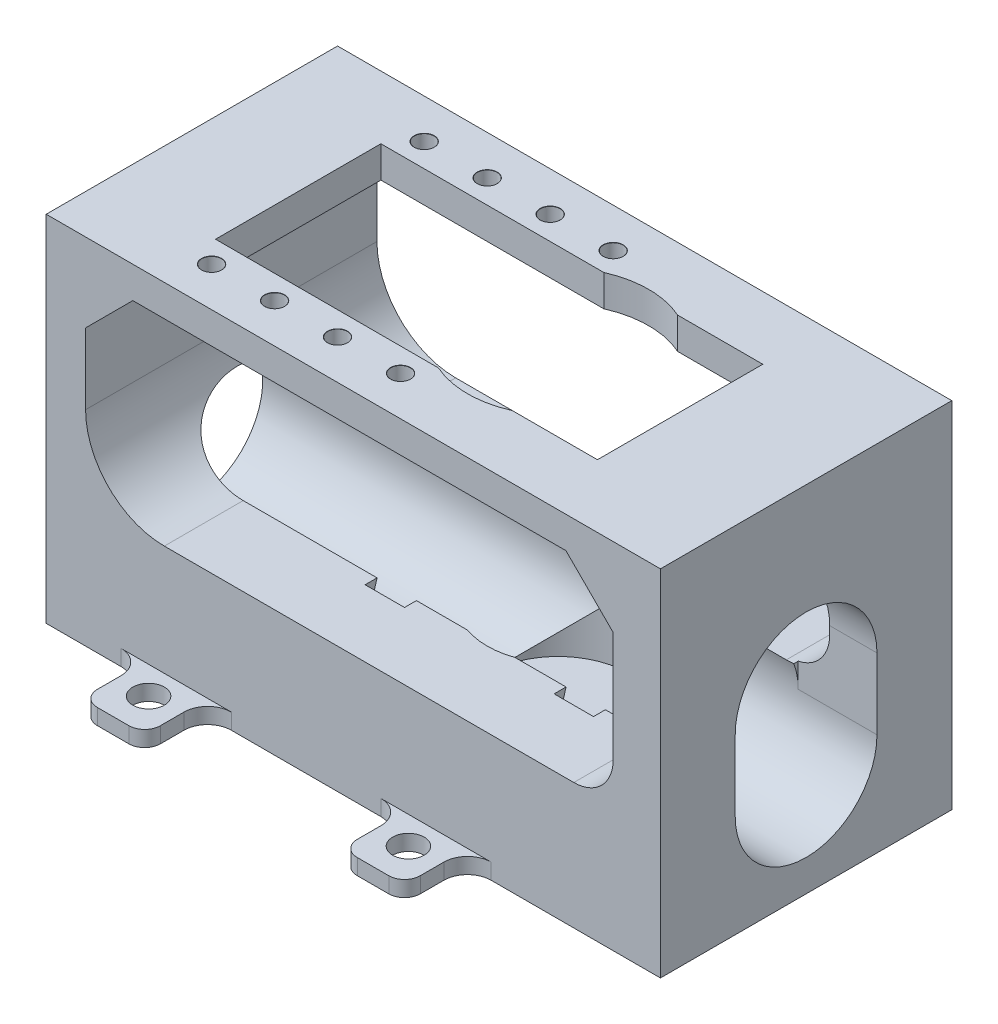
SolidWorks part; units mm, degrees
ref_plane "Front Plane" through (0, 0, 0) normal (0, 0, 1) x (1, 0, 0)
ref_plane "Top Plane" through (0, 0, 0) normal (0, 1, 0) x (1, 0, 0)
ref_plane "Right Plane" through (0, 0, 0) normal (1, 0, 0) x (0, 0, -1)
sketch "Sketch1" plane through (0, 0, 0) normal (0, 1, 0) x (1, 0, 0)
  line L1 (0, 0) -> (78, 0)
  line L2 (0, 0) -> (0, 37)
  line L3 (0, 37) -> (78, 37)
  line L4 (78, 0) -> (78, 37)
extrude "Boss-Extrude2" add sketch "Sketch1" along normal blind 2
sketch "Sketch4" plane through (0, 2, 0) normal (0, 1, 0) x (1, 0, 0)
  line L0 (78, 37) -> (0, 37) construction
  line L1 (0, 0) -> (5, 0)
  line L2 (0, 0) -> (0, 37)
  line L3 (0, 37) -> (5, 37)
  line L4 (5, 0) -> (5, 37)
extrude "Boss-Extrude3" add sketch "Sketch4" along normal blind 43
sketch "Sketch5" plane through (0, 2, 0) normal (0, 1, 0) x (1, 0, 0)
  line L0 (78, 37) -> (5, 37) construction
  line L1 (78, 0) -> (72, 0)
  line L2 (78, 0) -> (78, 37)
  line L3 (78, 37) -> (72, 37)
  line L4 (72, 0) -> (72, 37)
extrude "Boss-Extrude4" add sketch "Sketch5" along normal blind 43
sketch "Sketch6" plane through (0, 2, 0) normal (0, 1, 0) x (1, 0, 0)
  line L0 (72, 37) -> (72, 0) construction
  line L1 (5, 0) -> (72, 0)
  line L2 (5, 0) -> (5, 37)
  line L3 (5, 37) -> (72, 37)
  line L4 (72, 0) -> (72, 37)
extrude "Boss-Extrude5" add sketch "Sketch6" along normal blind 14 contours L2 L1 L4 L3
sketch "Sketch11" plane through (5, 0, 0) normal (1, 0, 0) x (0, 0, -1)
  line L1 (0, 41) -> (8, 41)
  line L2 (0, 41) -> (0, 45)
  line L3 (0, 45) -> (8, 45)
  line L4 (8, 41) -> (8, 45)
extrude "Boss-Extrude7" add sketch "Sketch11" along normal blind 67
sketch "Sketch14" plane through (72, 0, 0) normal (-1, 0, 0) x (0, 0, 1)
  line L1 (-37, 41) -> (-29, 41)
  line L2 (-37, 41) -> (-37, 45)
  line L3 (-37, 45) -> (-29, 45)
  line L4 (-29, 41) -> (-29, 45)
extrude "Boss-Extrude8" add sketch "Sketch14" along normal blind 67
sketch "Sketch15" plane through (0, 0, 0) normal (0, 0, 1) x (1, 0, 0)
  line L1 (0, 0) -> (78, 0) construction
  line L5 (12.5, 0) -> (12.5, 2)
  line L6 (12.5, 0) -> (20.5, 0)
  line L7 (12.5, 0) -> (12.5, 2)
  line L8 (12.5, 2) -> (20.5, 2)
  line L9 (20.5, 0) -> (20.5, 2)
  line L11 (20.5, 2) -> (20.5, 0)
  line L13 (45.5, 2) -> (45.5, 0)
  line L15 (45.5, 2) -> (53.5, 2)
  line L16 (45.5, 2) -> (45.5, 0)
  line L17 (45.5, 0) -> (53.5, 0)
  line L18 (53.5, 2) -> (53.5, 0)
  line M13 (0, 0) -> (78, 0)
extrude "Boss-Extrude9" add sketch "Sketch15" along normal blind 8 contours L9 L8 L5 M13 | L18 L15 L13 M13 region at (49.5, 1, 0) region at (16.5, 1, 0)
sketch "Sketch16" plane through (0, 0, -37) normal (0, 0, -1) x (-1, 0, 0)
  line L0 (-78, 0) -> (0, 0) construction
  line L5 (-12.5, 2) -> (-20.5, 2)
  line L6 (-12.5, 2) -> (-12.5, 0)
  line L7 (-12.5, 0) -> (-20.5, 0)
  line L8 (-20.5, 2) -> (-20.5, 0)
  line L18 (-45.5, 2) -> (-53.5, 2)
  line L19 (-45.5, 2) -> (-45.5, 0)
  line L20 (-45.5, 0) -> (-53.5, 0)
  line L21 (-53.5, 2) -> (-53.5, 0)
extrude "Boss-Extrude10" add sketch "Sketch16" along normal blind 8
sketch "Sketch18" plane through (0, 45, 0) normal (0, 1, 0) x (1, 0, 0)
  circle A0 centre (16, 32) radius 2
  circle A1 centre (24, 32) radius 2
  circle A2 centre (32, 32) radius 2
  circle A3 centre (40, 32) radius 2
  circle A4 centre (16, 5) radius 2
  circle A5 centre (24, 5) radius 2
  circle A6 centre (32, 5) radius 2
  circle A7 centre (40, 5) radius 2
sketch "Sketch20" plane through (0, 2, 0) normal (0, 1, 0) x (1, 0, 0)
  circle A0 centre (16.5, -3.5) radius 2
  circle A1 centre (49.5, -3.5) radius 2
  circle A2 centre (49.5, 40.5) radius 2
  circle A3 centre (16.5, 40.5) radius 2
extrude "Cut-Extrude2" cut sketch "Sketch20" against normal blind 3
fillet "Fillet5" radius 2 1 edges at (20.5, 1, 8)
fillet "Fillet6" radius 2 1 edges at (12.5, 1, 8)
fillet "Fillet7" radius 2 1 edges at (45.5, 1, 8)
fillet "Fillet8" radius 2 1 edges at (53.5, 1, 8)
fillet "Fillet9" radius 2 1 edges at (53.5, 1, -45)
fillet "Fillet10" radius 2 1 edges at (45.5, 1, -45)
fillet "Fillet11" radius 2 1 edges at (20.5, 1, -45)
fillet "Fillet12" radius 2 1 edges at (12.5, 1, -45)
fillet "Fillet13" radius 3 1 edges at (12.5, 1, -37)
fillet "Fillet14" radius 3 1 edges at (20.5, 1, -37)
fillet "Fillet15" radius 3 1 edges at (45.5, 1, -37)
fillet "Fillet16" radius 3 1 edges at (53.5, 1, -37)
fillet "Fillet17" radius 3 1 edges at (12.5, 1, 0)
fillet "Fillet18" radius 3 1 edges at (20.5, 1, 0)
fillet "Fillet19" radius 3 1 edges at (45.5, 1, 0)
fillet "Fillet20" radius 3 1 edges at (53.5, 1, 0)
sketch "Sketch24" plane through (5, 0, 0) normal (1, 0, 0) x (0, 0, -1)
  line L1 (8, 45) -> (29, 45)
  line L2 (8, 45) -> (8, 41)
  line L3 (8, 41) -> (29, 41)
  line L4 (29, 45) -> (29, 41)
extrude "Boss-Extrude11" add sketch "Sketch24" along normal blind 8.5
sketch "Sketch25" plane through (72, 0, 0) normal (-1, 0, 0) x (0, 0, 1)
  line L1 (-29, 45) -> (-8, 45)
  line L2 (-29, 45) -> (-29, 41)
  line L3 (-29, 41) -> (-8, 41)
  line L4 (-8, 45) -> (-8, 41)
extrude "Boss-Extrude12" add sketch "Sketch25" along normal blind 10
sketch "Sketch21" plane through (0, 45, 0) normal (0, 1, 0) x (1, 0, 0)
  circle A0 centre (46.5, 18.5) radius 11.5
extrude "Cut-Extrude6" cut sketch "Sketch21" against normal blind 4 contours A0
sketch "Sketch27" plane through (0, 0, 0) normal (-1, 0, 0) x (0, 0, 1)
  circle A0 centre (-18.5, 13) radius 9
  point P2 (0, 0)
extrude "Cut-Extrude7" cut sketch "Sketch27" against normal blind 78
sketch "Sketch28" plane through (0, 16, 0) normal (0, 1, 0) x (1, 0, 0)
  circle A0 centre (46.5, 18.5) radius 9
extrude "Cut-Extrude8" cut sketch "Sketch28" against normal blind 12
fillet "Fillet24" radius 10 2 edges at (5, 16, -5.0074) (5, 16, -31.9926)
sketch "Sketch33" plane through (0, 16, 0) normal (0, 1, 0) x (1, 0, 0)
  line L21 (37, 12) -> (32, 12)
  line L22 (37, 12) -> (37, 8.5)
  line L23 (37, 8.5) -> (32, 8.5)
  line L24 (32, 12) -> (32, 8.5)
  line L25 (61, 12) -> (56, 12)
  line L26 (61, 12) -> (61, 8.5)
  line L27 (61, 8.5) -> (56, 8.5)
  line L28 (56, 12) -> (56, 8.5)
extrude "Cut-Extrude10" cut sketch "Sketch33" against normal blind 11
sketch "Sketch35" plane through (72, 0, 0) normal (-1, 0, 0) x (0, 0, 1)
  circle A0 centre (-18.5, 22) radius 9
  circle A1 centre (-18.5, 13) radius 9 construction
extrude "Cut-Extrude12" cut sketch "Sketch35" against normal blind 8
fillet "Fillet25" radius 5 1 edges at (72, 16, -5.0074)
fillet "Fillet26" radius 5 1 edges at (72, 16, -31.9926)
chamfer "Chamfer1" distance 6 angle 45 1 edges at (72, 41, -18.5)
chamfer "Chamfer2" distance 6 angle 45 1 edges at (5, 41, -18.5)
hole_wizard "Tap Drill for M3 Tap1" positions "Sketch36" profile "Sketch37" hole size "M3" standard "IS" end condition up to next
sketch "Sketch36" plane through (0, 45, 0) normal (0, 1, 0) x (1, 0, 0)
  point P0 (16, 32)
  point P3 (24, 32)
  point P6 (32, 32)
  point P9 (40, 32)
  point P12 (16, 5)
  point P15 (24, 5)
  point P18 (32, 5)
  point P21 (40, 5)
sketch "Sketch37" plane through (16, 45, -32) normal (1, 0, 0) x (0, 0, 1)
  line L0 (0, 0) -> (0, 4)
  line L1 (0, 4) -> (1.25, 4)
  line L2 (1.25, 4) -> (1.25, 0.021)
  line L3 (1.25, 0.021) -> (1.275, 0)
  line L5 (1.275, 0) -> (0, 0)
  line L6 (-1.25, 0.021) -> (-1.275, 0) construction
  line L11 (0, -6.35) -> (0, 107.95) construction
  dimension "Thru Hole Dia." = 2.5
  dimension "Thru Hole Depth" = 4
  dimension "Near C'Sink Dia." = 2.55
  dimension "Near C'Sink Angle" = 100
sketch "Sketch39" plane through (78, 0, 0) normal (1, 0, 0) x (0, 0, -1)
  line L1 (9.5, 22) -> (27.5, 22)
  line L2 (9.5, 22) -> (9.5, 13)
  line L3 (9.5, 13) -> (27.5, 13)
  line L4 (27.5, 22) -> (27.5, 13)
  arc A0 (26.2942, 17.5) -> (10.7058, 17.5) centre (18.5, 22) ccw construction
  arc A1 (10.7058, 17.5) -> (26.2942, 17.5) centre (18.5, 13) ccw construction
extrude "Cut-Extrude13" cut sketch "Sketch39" against normal blind 10
